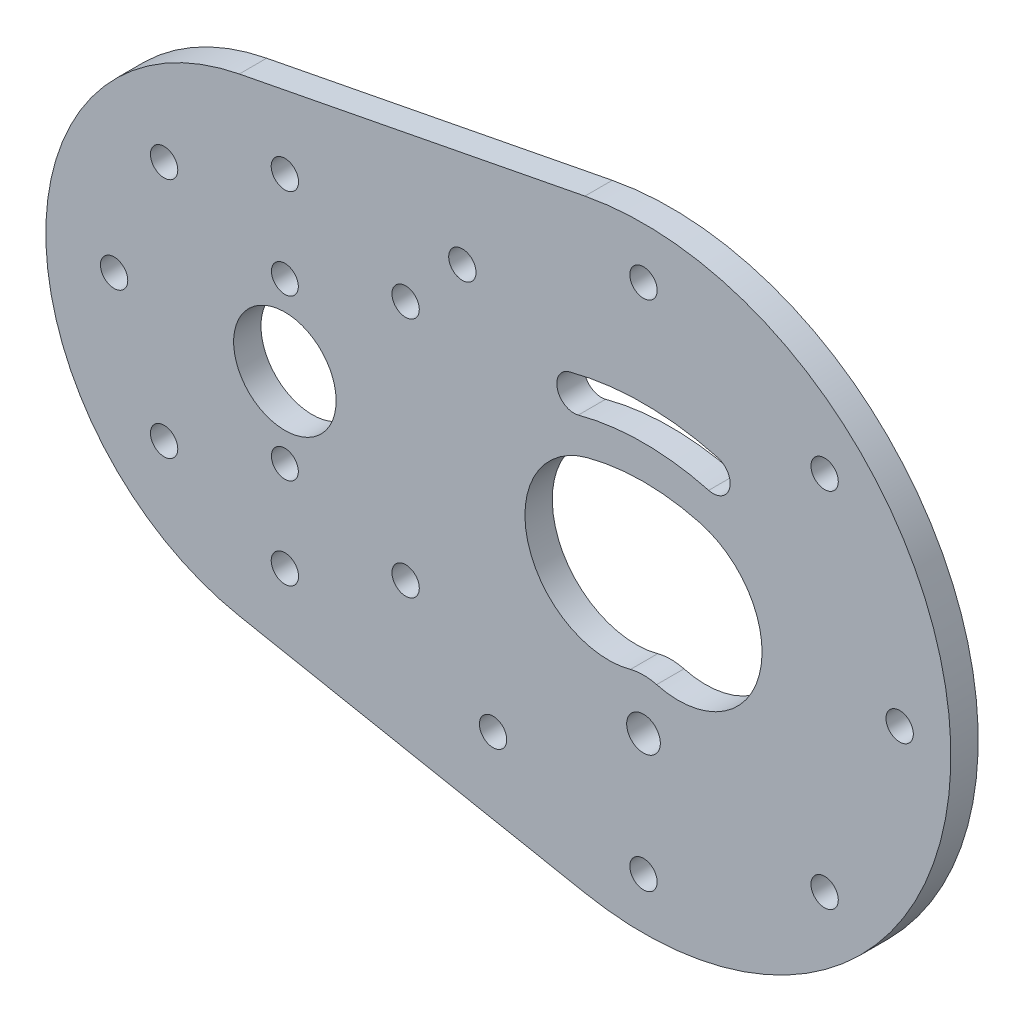
SolidWorks part; units mm, degrees
ref_plane "Front Plane" through (0, 0, 0) normal (0, 0, 1) x (1, 0, 0)
ref_plane "Top Plane" through (0, 0, 0) normal (0, 1, 0) x (1, 0, 0)
ref_plane "Right Plane" through (0, 0, 0) normal (1, 0, 0) x (0, 0, -1)
sketch "Sketch1" plane through (0, 0, 0) normal (0, 0, 1) x (1, 0, 0)
  line L0 (0, 0) -> (0, 36.4546) construction
  line L1 (0, 0) -> (-10.2847, 38.3829) construction
  line L2 (-33.3375, 12.5) -> (0, 12.5) construction
  line L4 (-91.5313, 56.95) -> (35.4687, 56.95)
  line L5 (-91.5313, 56.95) -> (-91.5313, -31.95)
  line L6 (-91.5313, -31.95) -> (35.4687, -31.95)
  line L7 (35.4687, 56.95) -> (35.4687, -31.95)
  line L8 (-91.5313, 56.95) -> (35.4687, -31.95) construction
  line L9 (-91.5313, -31.95) -> (35.4687, 56.95) construction
  arc A0 (5.2502, 19.5939) -> (1.2203, 4.5542) centre (3.2352, 12.0741) cw
  arc A1 (5.2502, 19.5939) -> (-5.2502, 19.5939) centre (0, 0) ccw
  circle A2 centre (0, 12.5) radius 12.5 construction
  circle A3 centre (0, 0) radius 1.5649
  arc A4 (10.8253, 6.25) -> (-10.8253, 6.25) centre (0, 0) ccw construction
  arc A5 (1.2203, 4.5542) -> (-1.2203, 4.5542) centre (0, 0) ccw
  arc A6 (-5.2502, 19.5939) -> (-1.2203, 4.5542) centre (-3.2352, 12.0741) ccw
  circle A7 centre (0, 25) radius 1.5875 construction
  arc A8 (6.8814, 25.6816) -> (-6.8814, 25.6816) centre (0, 0) ccw
  arc A9 (6.0596, 22.6147) -> (-6.0596, 22.6147) centre (0, 0) ccw
  circle A10 centre (0, 0) radius 25 construction
  arc A11 (-6.8814, 25.6816) -> (-6.0596, 22.6147) centre (-6.4705, 24.1481) ccw
  arc A12 (6.8814, 25.6816) -> (6.0596, 22.6147) centre (6.4705, 24.1481) cw
  circle A13 centre (-33.3375, 12.5) radius 4.7625
  circle A14 centre (-33.3375, 12.5) radius 25.4 construction
  point P0 (0, 0)
  point P18 (-28.0313, 12.5)
  dimension "D4" = 25
  dimension "D6" = 50.8
  dimension "D2" = 3.175
  dimension "D3" = 9.525
  dimension "D9" = 7.7851
  dimension "D1" = 15
  dimension "D5" = 33.3375
  dimension "D7" = 88.9
  dimension "D8" = 127
extrude "Boss-Extrude1" add sketch "Sketch1" along normal blind 2.54
sketch "Sketch2" plane through (0, 0, 2.54) normal (0, 0, 1) x (1, 0, 0)
  line L0 (-33.3375, 12.5) -> (43.934, 12.5) construction
  line L1 (0, 0) -> (0, 70.9306) construction
  line L2 (-37.5708, 34.3181) -> (-5.4429, 40.5518)
  line L3 (-37.5708, -9.3181) -> (-5.4429, -15.5518)
  line L5 (-107.0175, 80.3674) -> (70.5021, 80.3674)
  line L6 (-107.0175, 80.3674) -> (-107.0175, -46.3508)
  line L7 (-107.0175, -46.3508) -> (70.5021, -46.3508)
  line L8 (70.5021, 80.3674) -> (70.5021, -46.3508)
  arc A0 (-5.4429, -15.5518) -> (-5.4429, 40.5518) centre (0, 12.5) ccw
  arc A1 (-37.5708, 34.3181) -> (-37.5708, -9.3181) centre (-33.3375, 12.5) ccw
  dimension "D1" = 57.15
  dimension "D2" = 44.45
extrude "Cut-Extrude1" cut sketch "Sketch2" against normal through all
sketch "Sketch4" plane through (0, 0, 2.54) normal (0, 0, 1) x (1, 0, 0)
  line L0 (-33.3375, 12.5) -> (35.849, 12.5) construction
  line L1 (0, 0) -> (0, 48.1146) construction
  circle A0 centre (-33.3375, 12.5) radius 15.875 construction
  circle A1 centre (0, 12.5) radius 23.8125 construction
  circle A2 centre (-33.3375, 28.375) radius 1.27
  circle A3 centre (0, 36.3125) radius 1.27
  circle A4 centre (-22.1122, 23.7253) radius 1.27
  circle A5 centre (-17.4625, 12.5) radius 1.27 [skipped]
  circle A6 centre (-13.9821, -6.8554) radius 1.27
  circle A7 centre (-22.1122, 1.2747) radius 1.27
  circle A8 centre (-33.3375, -3.375) radius 1.27
  circle A9 centre (-44.5628, 1.2747) radius 1.27
  circle A10 centre (-49.2125, 12.5) radius 1.27
  circle A11 centre (16.838, 29.338) radius 1.27
  circle A12 centre (23.8125, 12.5) radius 1.27
  circle A13 centre (16.838, -4.338) radius 1.27
  circle A14 centre (0, -11.3125) radius 1.27
  circle A15 centre (-44.5628, 23.7253) radius 1.27
  circle A16 centre (-23.8125, 12.5) radius 1.27 [skipped]
  circle A17 centre (-16.838, 29.338) radius 1.27
  circle A18 centre (-16.838, -4.338) radius 1.27 [skipped]
  dimension "D1" = 47.625
  dimension "D2" = 31.75
  dimension "D3" = 2.54
  dimension "D4" = 2.54
  dimension "D6" = 8
  dimension "D5" = 8
extrude "Cut-Extrude2" cut sketch "Sketch4" against normal through all
sketch "Sketch5" plane through (0, 0, 2.54) normal (0, 0, 1) x (1, 0, 0)
  circle A0 centre (-33.3375, 12.5) radius 7.4422 construction
  circle A1 centre (-33.3375, 19.9422) radius 1.25
  circle A2 centre (-33.3375, 5.0578) radius 1.25
  dimension "D1" = 14.8844
  dimension "D2" = 2.5
  dimension "D3" = 2.5
extrude "Cut-Extrude3" cut sketch "Sketch5" against normal through all
